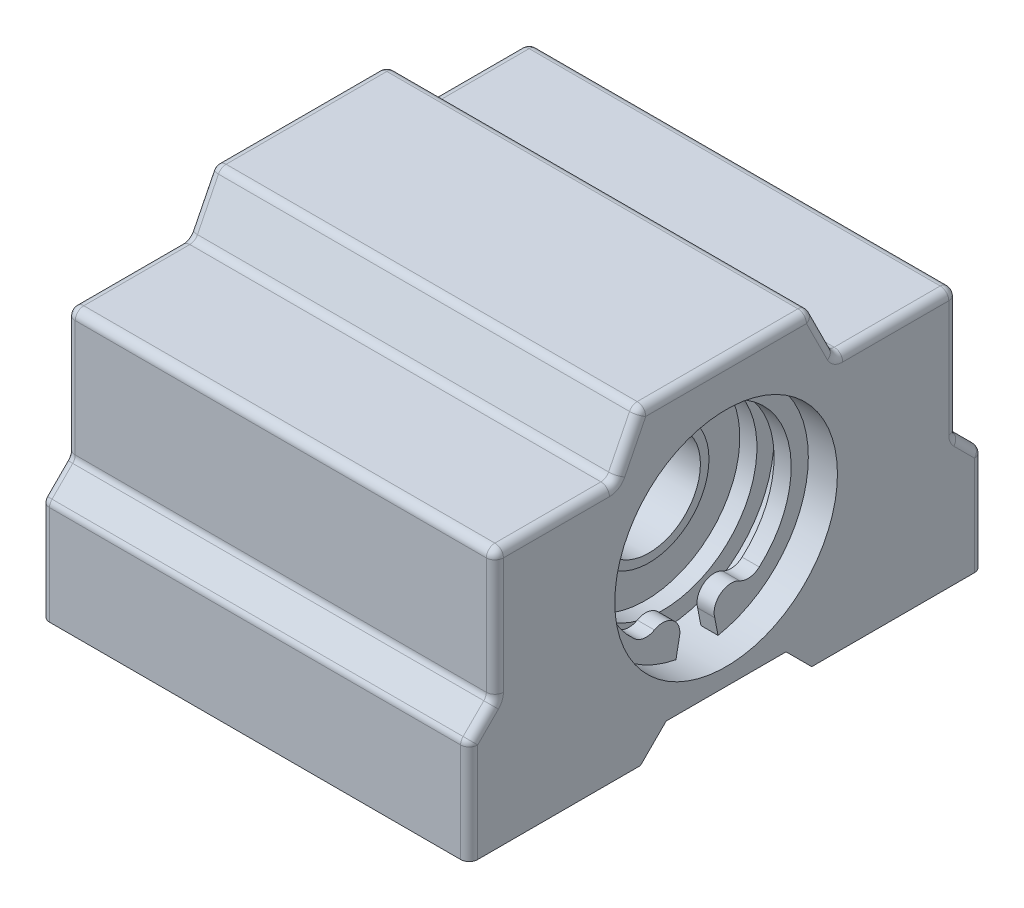
SolidWorks part; units mm, degrees
ref_plane "Front Plane" through (0, 0, 0) normal (0, 0, 1) x (1, 0, 0)
ref_plane "Top Plane" through (0, 0, 0) normal (0, 1, 0) x (1, 0, 0)
ref_plane "Right Plane" through (0, 0, 0) normal (1, 0, 0) x (0, 0, -1)
sketch "Sketch1" plane through (0, 0, 0) normal (1, 0, 0) x (0, 0, -1)
  line L1 (-5, -9) -> (-3.5, -7.5)
  line L2 (-3.5, -7.5) -> (3.5, -7.5)
  line L3 (3.5, -7.5) -> (5, -9)
  line L4 (5, -9) -> (15, -9)
  line L6 (15, -3) -> (13.5, -1.5)
  line L8 (13.5, 6) -> (6.5, 6)
  line L9 (6.5, 6) -> (5, 9)
  line L10 (5, 9) -> (-5, 9)
  line L11 (-5, 9) -> (-6.5, 6)
  line L12 (-6.5, 6) -> (-13.5, 6)
  line L15 (-15, -3) -> (-15, -9)
  line L16 (0, -7.5) -> (0, 9) construction
  line L17 (-16.278, 0) -> (14.0247, 0) construction
  line L18 (-15, -9) -> (-5, -9)
  line L19 (15, -3) -> (15, -9)
  line L20 (-13.5, -1.5) -> (-13.5, 6)
  line L21 (13.5, -1.5) -> (13.5, 6)
  line L22 (-10, 6) -> (-10, -9) construction
  line L23 (-10, -9) -> (10, 6) construction
  line L24 (10, 6) -> (10, -9) construction
  line L25 (-15, -3) -> (-13.5, -1.5)
  circle A0 centre (0, 0) radius 6.5
  circle A1 centre (0, 0) radius 5.5
  circle A2 centre (0, 0) radius 3
  point P18 (0, 9)
  point P23 (13.202, -3)
  point P24 (13.5573, -1.1927)
  point P27 (-6.5, 6)
  point P29 (-15, -9)
  point P30 (-15, -3)
  point P31 (-13.5, -1.5)
  point P32 (13.5, -1.5)
  point P33 (13.5, 6)
  point P34 (3.4544, -7.6715)
  point P35 (-5.6345, -9)
  point P36 (-3.5, -7.5)
  point P41 (-6.5, 6)
  point P42 (-6.5, 6)
  point P45 (-5, 9)
  dimension "D1" = 30
  dimension "D9" = 1.5
  dimension "D3" = 9
  dimension "D13" = 13
  dimension "D12" = 6
  dimension "D2" = 15
  dimension "D4" = 6
  dimension "D5" = 18
  dimension "D6" = 20
  dimension "D7" = 1.5
  dimension "D8" = 10
  dimension "D10" = 10
  dimension "D11" = 1
extrude "Boss-Extrude1" add sketch "Sketch1" along normal blind 25 contours L25 L15 L18 L1 L2 L3 L4 L19 L6 L21 L8 L9 L10 L11 L12 L20 A0 region at (0, -8.6501, 10)
extrude "Extrude-Thin1" add sketch "Sketch1<4>" along normal blind 20 from offset 0.5 separate body thin contours A2 thin type one direction wall 0.5
sketch "Sketch1<4>" plane through (0, 0, 0) normal (1, 0, 0) x (0, 0, -1) same geometry as "Sketch1"
extrude "Boss-Extrude2" add sketch "Sketch1<5>" along normal blind 19.5 from offset 0.8 contours A1 A2 region at (0, 0, 5.3444)
sketch "Sketch1<5>" plane through (0, 0, 0) normal (1, 0, 0) x (0, 0, -1) same geometry as "Sketch1"
extrude "Boss-Extrude3" add sketch "Sketch1<6>" along normal blind 21 from offset 0.3 contours A0 A1 region at (0, 0, 6.3162)
sketch "Sketch1<6>" plane through (0, 0, 0) normal (1, 0, 0) x (0, 0, -1) same geometry as "Sketch1"
ref_plane "Plane1" through (21.3, 0, 0) normal (1, 0, 0) x (0, 0, -1)
sketch "Sketch3" plane through (21.3, 0, 0) normal (1, 0, 0) x (0, 0, -1)
  line L0 (0, 0) -> (0, -50000) construction
  line L1 (-1.0393, -5.4009) -> (-1.2282, -6.3829)
  line L2 (1.0393, -5.4009) -> (1.2282, -6.3829)
  circle A0 centre (0, 0) radius 6.5 construction
  arc A1 (1.2282, -6.3829) -> (-1.2282, -6.3829) centre (0, 0) ccw
  circle A2 centre (0, 0) radius 5.5 construction
  arc A3 (0, -5.5) -> (1.0393, -5.4009) centre (0, 0) ccw
  arc A4 (-1.0393, -5.4009) -> (-2.4872, -4.2502) centre (-2, -5.1235) ccw
  circle A5 centre (-2, -5.1235) radius 0.25
  arc A6 (-2.2308, -5.0273) -> (-1.7651, -5.2091) centre (0, 0) ccw
  arc A7 (-2.4872, -4.2502) -> (-3.6353, -4.1273) centre (-2.9744, -3.3769) cw
  arc A8 (2.4872, -4.2502) -> (3.6353, -4.1273) centre (2.9744, -3.3769) ccw
  circle A10 centre (2, -5.1235) radius 0.25
  arc A11 (1.0393, -5.4009) -> (2.4872, -4.2502) centre (2, -5.1235) cw
  arc A13 (3.6353, -4.1273) -> (-3.6353, -4.1273) centre (0, 0) ccw
  point P12 (-1.1793, -6.3921)
  dimension "D1" = 0.5
  dimension "D2" = 2
  dimension "D3" = 1
  dimension "D4" = 2
extrude "Boss-Extrude4" add sketch "Sketch3" along normal blind 1 from offset 1 contours A11 A8 A13 A7 A4 L1 A1 L2
fillet "Fillet1" radius 0.5 32 edges at (12.5, -1.5, -13.5) (12.5, -1.5, 13.5) (12.5, -3, 15) (12.5, -3, -15) (12.5, 6, -6.5) (12.5, 6, 6.5) (12.5, 9, 5) (12.5, 9, -5) (12.5, 6, -13.5) (12.5, 6, 13.5) (25, 7.5, -5.75) (25, 7.5, 5.75) (25, 2.25, 13.5) (0, -2.25, 14.25) (0, 7.5, 5.75) (25, -2.25, -14.25) (25, -6, -15) (25, 2.25, -13.5) (25, 9, 0) (25, 6, -10) (25, 6, 10) (25, -2.25, 14.25) (25, -6, 15) (0, -6, -15) (0, -2.25, -14.25) (0, 2.25, -13.5) (0, 7.5, -5.75) (0, 6, -10) (0, 9, 0) (0, -6, 15) (0, 2.25, 13.5) (0, 6, 10)
